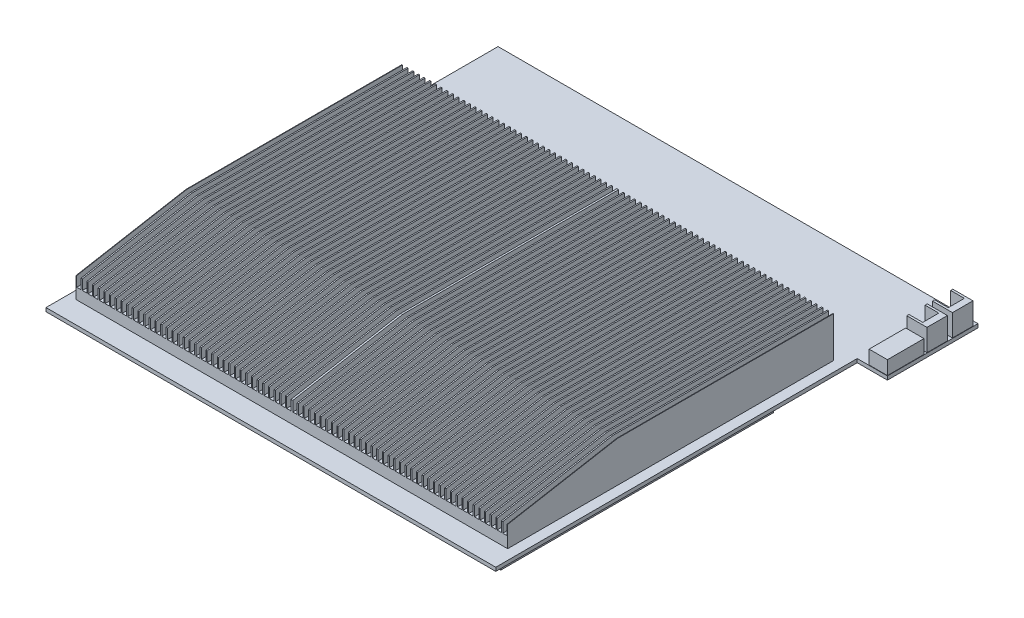
SolidWorks part; units mm, degrees
ref_plane "Front Plane" through (0, 0, 0) normal (0, 0, 1) x (1, 0, 0)
ref_plane "Top Plane" through (0, 0, 0) normal (0, 1, 0) x (1, 0, 0)
ref_plane "Right Plane" through (0, 0, 0) normal (1, 0, 0) x (0, 0, -1)
sketch "Sketch1" plane through (0, 0, 0) normal (0, 1, 0) x (1, 0, 0)
  line L0 (0, 0) -> (0, 247)
  line L1 (0, 247) -> (262.25, 247)
  line L2 (262.25, 247) -> (262.25, 197.5)
  line L3 (262.25, 197.5) -> (245.75, 197.5)
  line L4 (245.75, 197.5) -> (245.75, 0)
  line L5 (245.75, 0) -> (0, 0)
  dimension "D1" = 247
  dimension "D2" = 245.75
  dimension "D3" = 49.5
  dimension "D4" = 16.5
extrude "Boss-Extrude1" add sketch "Sketch1" along normal blind 2
sketch "Sketch2" plane through (0, 2, 0) normal (0, 1, 0) x (1, 0, 0)
  line L0 (245.75, 0) -> (245.75, 197.5) construction
  line L1 (4.5, 190) -> (240.25, 190)
  line L2 (4.5, 190) -> (4.5, 12)
  line L3 (4.5, 12) -> (240.25, 12)
  line L4 (240.25, 190) -> (240.25, 12)
  line L5 (4.5, 190) -> (240.25, 12) construction
  line L6 (4.5, 12) -> (240.25, 190) construction
  line L7 (0, 0) -> (245.75, 0) construction
  line L8 (0, 247) -> (0, 0) construction
  line L9 (262.25, 247) -> (0, 247) construction
  point P4 (122.375, 101)
  dimension "D1" = 5.5
  dimension "D2" = 12
  dimension "D3" = 4.5
  dimension "D4" = 57
extrude "Boss-Extrude2" add sketch "Sketch2" along normal blind 22.2
sketch "Sketch3" plane through (240.25, 0, 0) normal (1, 0, 0) x (0, 0, -1)
  line L0 (12, 13.5) -> (72, 24.2)
  line L1 (12, 24.2) -> (12, 2) construction
  line L2 (12, 24.2) -> (190, 24.2) construction
  line L3 (72, 24.2) -> (12, 24.2)
  line L4 (12, 24.2) -> (12, 13.5)
  dimension "D1" = 60
  dimension "D2" = 10.7
extrude "Cut-Extrude1" cut sketch "Sketch3" against normal up to surface (235.75 mm away) up to face at (4.5, 13.1, -101)
sketch "Sketch5" plane through (0, 0, 0) normal (0, -1, 0) x (1, 0, 0)
  line L0 (7.9691, -163.75) -> (7.9691, -14.75)
  line L6 (233.7585, -14.75) -> (233.7585, -163.75)
  line L9 (7.9691, -163.75) -> (67.4691, -163.75)
  line L10 (67.4691, -163.75) -> (67.4691, -196.5)
  line L11 (67.4691, -196.5) -> (174.2585, -196.5)
  line L12 (174.2585, -196.5) -> (174.2585, -163.75)
  line L13 (174.2585, -163.75) -> (233.7585, -163.75)
  line L14 (233.7585, -14.75) -> (7.9691, -14.75)
  line L15 (0, 0) -> (245.75, 0) construction
  line L16 (262.25, -247) -> (0, -247) construction
  line L18 (122.5508, -211.25) -> (149.8508, -211.25)
  line L19 (122.5508, -211.25) -> (122.5508, -241.5)
  line L20 (122.5508, -241.5) -> (149.8508, -241.5)
  line L21 (149.8508, -211.25) -> (149.8508, -241.5)
  line L22 (122.5508, -211.25) -> (149.8508, -241.5) construction
  line L23 (122.5508, -241.5) -> (149.8508, -211.25) construction
  point P16 (136.2008, -226.375)
  dimension "D1" = 14.75
  dimension "D2" = 50.5
  dimension "D3" = 83.25
  dimension "D4" = 59.5
  dimension "D5" = 5.5
  dimension "D6" = 14.75
  dimension "D7" = 27.3
extrude "Boss-Extrude4" add sketch "Sketch5" along normal blind 12.75
sketch "Sketch6" plane through (0, 0, -190) normal (0, 0, -1) x (-1, 0, 0)
  line L0 (-122.375, 24.2) -> (-122.375, 2) construction
  line L1 (-240.25, 24.2) -> (-4.5, 24.2) construction
  line L2 (-240.25, 2) -> (-4.5, 2) construction
  line L3 (-262.25, 2) -> (0, 2) construction
  line L4 (-122.875, 24.2) -> (-125.275, 24.2)
  line L5 (-122.875, 24.2) -> (-122.875, 8)
  line L6 (-122.875, 8) -> (-125.275, 8)
  line L7 (-125.275, 24.2) -> (-125.275, 8)
  line L8 (-122.875, 24.2) -> (-125.275, 8) construction
  line L9 (-122.875, 8) -> (-125.275, 24.2) construction
  line L10 (-121.875, 8) -> (-119.475, 24.2) construction
  line L11 (-121.875, 24.2) -> (-119.475, 8) construction
  line L12 (-119.475, 24.2) -> (-119.475, 8)
  line L13 (-121.875, 8) -> (-119.475, 8)
  line L14 (-121.875, 24.2) -> (-121.875, 8)
  line L15 (-121.875, 24.2) -> (-119.475, 24.2)
  line L16 (-125.975, 24.2) -> (-128.375, 24.2)
  line L17 (-125.975, 24.2) -> (-125.975, 8)
  line L18 (-125.975, 8) -> (-128.375, 8)
  line L19 (-128.375, 24.2) -> (-128.375, 8)
  line L20 (-125.975, 24.2) -> (-128.375, 8) construction
  line L21 (-125.975, 8) -> (-128.375, 24.2) construction
  line L22 (-129.075, 24.2) -> (-131.475, 24.2)
  line L23 (-129.075, 24.2) -> (-129.075, 8)
  line L24 (-129.075, 8) -> (-131.475, 8)
  line L25 (-131.475, 24.2) -> (-131.475, 8)
  line L26 (-129.075, 24.2) -> (-131.475, 8) construction
  line L27 (-129.075, 8) -> (-131.475, 24.2) construction
  line L28 (-132.175, 24.2) -> (-134.575, 24.2)
  line L29 (-132.175, 24.2) -> (-132.175, 8)
  line L30 (-132.175, 8) -> (-134.575, 8)
  line L31 (-134.575, 24.2) -> (-134.575, 8)
  line L32 (-132.175, 24.2) -> (-134.575, 8) construction
  line L33 (-132.175, 8) -> (-134.575, 24.2) construction
  line L34 (-135.275, 24.2) -> (-137.675, 24.2)
  line L35 (-135.275, 24.2) -> (-135.275, 8)
  line L36 (-135.275, 8) -> (-137.675, 8)
  line L37 (-137.675, 24.2) -> (-137.675, 8)
  line L38 (-135.275, 24.2) -> (-137.675, 8) construction
  line L39 (-135.275, 8) -> (-137.675, 24.2) construction
  line L40 (-138.375, 24.2) -> (-140.775, 24.2)
  line L41 (-138.375, 24.2) -> (-138.375, 8)
  line L42 (-138.375, 8) -> (-140.775, 8)
  line L43 (-140.775, 24.2) -> (-140.775, 8)
  line L44 (-138.375, 24.2) -> (-140.775, 8) construction
  line L45 (-138.375, 8) -> (-140.775, 24.2) construction
  line L46 (-141.475, 24.2) -> (-143.875, 24.2)
  line L47 (-141.475, 24.2) -> (-141.475, 8)
  line L48 (-141.475, 8) -> (-143.875, 8)
  line L49 (-143.875, 24.2) -> (-143.875, 8)
  line L50 (-141.475, 24.2) -> (-143.875, 8) construction
  line L51 (-141.475, 8) -> (-143.875, 24.2) construction
  line L52 (-144.575, 24.2) -> (-146.975, 24.2)
  line L53 (-144.575, 24.2) -> (-144.575, 8)
  line L54 (-144.575, 8) -> (-146.975, 8)
  line L55 (-146.975, 24.2) -> (-146.975, 8)
  line L56 (-144.575, 24.2) -> (-146.975, 8) construction
  line L57 (-144.575, 8) -> (-146.975, 24.2) construction
  line L58 (-147.675, 24.2) -> (-150.075, 24.2)
  line L59 (-147.675, 24.2) -> (-147.675, 8)
  line L60 (-147.675, 8) -> (-150.075, 8)
  line L61 (-150.075, 24.2) -> (-150.075, 8)
  line L62 (-147.675, 24.2) -> (-150.075, 8) construction
  line L63 (-147.675, 8) -> (-150.075, 24.2) construction
  line L64 (-150.775, 24.2) -> (-153.175, 24.2)
  line L65 (-150.775, 24.2) -> (-150.775, 8)
  line L66 (-150.775, 8) -> (-153.175, 8)
  line L67 (-153.175, 24.2) -> (-153.175, 8)
  line L68 (-150.775, 24.2) -> (-153.175, 8) construction
  line L69 (-150.775, 8) -> (-153.175, 24.2) construction
  line L70 (-153.875, 24.2) -> (-156.275, 24.2)
  line L71 (-153.875, 24.2) -> (-153.875, 8)
  line L72 (-153.875, 8) -> (-156.275, 8)
  line L73 (-156.275, 24.2) -> (-156.275, 8)
  line L74 (-153.875, 24.2) -> (-156.275, 8) construction
  line L75 (-153.875, 8) -> (-156.275, 24.2) construction
  line L76 (-156.975, 24.2) -> (-159.375, 24.2)
  line L77 (-156.975, 24.2) -> (-156.975, 8)
  line L78 (-156.975, 8) -> (-159.375, 8)
  line L79 (-159.375, 24.2) -> (-159.375, 8)
  line L80 (-156.975, 24.2) -> (-159.375, 8) construction
  line L81 (-156.975, 8) -> (-159.375, 24.2) construction
  line L82 (-160.075, 24.2) -> (-162.475, 24.2)
  line L83 (-160.075, 24.2) -> (-160.075, 8)
  line L84 (-160.075, 8) -> (-162.475, 8)
  line L85 (-162.475, 24.2) -> (-162.475, 8)
  line L86 (-160.075, 24.2) -> (-162.475, 8) construction
  line L87 (-160.075, 8) -> (-162.475, 24.2) construction
  line L88 (-163.175, 24.2) -> (-165.575, 24.2)
  line L89 (-163.175, 24.2) -> (-163.175, 8)
  line L90 (-163.175, 8) -> (-165.575, 8)
  line L91 (-165.575, 24.2) -> (-165.575, 8)
  line L92 (-163.175, 24.2) -> (-165.575, 8) construction
  line L93 (-163.175, 8) -> (-165.575, 24.2) construction
  line L94 (-166.275, 24.2) -> (-168.675, 24.2)
  line L95 (-166.275, 24.2) -> (-166.275, 8)
  line L96 (-166.275, 8) -> (-168.675, 8)
  line L97 (-168.675, 24.2) -> (-168.675, 8)
  line L98 (-166.275, 24.2) -> (-168.675, 8) construction
  line L99 (-166.275, 8) -> (-168.675, 24.2) construction
  line L100 (-169.375, 24.2) -> (-171.775, 24.2)
  line L101 (-169.375, 24.2) -> (-169.375, 8)
  line L102 (-169.375, 8) -> (-171.775, 8)
  line L103 (-171.775, 24.2) -> (-171.775, 8)
  line L104 (-169.375, 24.2) -> (-171.775, 8) construction
  line L105 (-169.375, 8) -> (-171.775, 24.2) construction
  line L106 (-172.475, 24.2) -> (-174.875, 24.2)
  line L107 (-172.475, 24.2) -> (-172.475, 8)
  line L108 (-172.475, 8) -> (-174.875, 8)
  line L109 (-174.875, 24.2) -> (-174.875, 8)
  line L110 (-172.475, 24.2) -> (-174.875, 8) construction
  line L111 (-172.475, 8) -> (-174.875, 24.2) construction
  line L112 (-175.575, 24.2) -> (-177.975, 24.2)
  line L113 (-175.575, 24.2) -> (-175.575, 8)
  line L114 (-175.575, 8) -> (-177.975, 8)
  line L115 (-177.975, 24.2) -> (-177.975, 8)
  line L116 (-175.575, 24.2) -> (-177.975, 8) construction
  line L117 (-175.575, 8) -> (-177.975, 24.2) construction
  line L118 (-178.675, 24.2) -> (-181.075, 24.2)
  line L119 (-178.675, 24.2) -> (-178.675, 8)
  line L120 (-178.675, 8) -> (-181.075, 8)
  line L121 (-181.075, 24.2) -> (-181.075, 8)
  line L122 (-178.675, 24.2) -> (-181.075, 8) construction
  line L123 (-178.675, 8) -> (-181.075, 24.2) construction
  line L124 (-181.775, 24.2) -> (-184.175, 24.2)
  line L125 (-181.775, 24.2) -> (-181.775, 8)
  line L126 (-181.775, 8) -> (-184.175, 8)
  line L127 (-184.175, 24.2) -> (-184.175, 8)
  line L128 (-181.775, 24.2) -> (-184.175, 8) construction
  line L129 (-181.775, 8) -> (-184.175, 24.2) construction
  line L130 (-184.875, 24.2) -> (-187.275, 24.2)
  line L131 (-184.875, 24.2) -> (-184.875, 8)
  line L132 (-184.875, 8) -> (-187.275, 8)
  line L133 (-187.275, 24.2) -> (-187.275, 8)
  line L134 (-184.875, 24.2) -> (-187.275, 8) construction
  line L135 (-184.875, 8) -> (-187.275, 24.2) construction
  line L136 (-187.975, 24.2) -> (-190.375, 24.2)
  line L137 (-187.975, 24.2) -> (-187.975, 8)
  line L138 (-187.975, 8) -> (-190.375, 8)
  line L139 (-190.375, 24.2) -> (-190.375, 8)
  line L140 (-187.975, 24.2) -> (-190.375, 8) construction
  line L141 (-187.975, 8) -> (-190.375, 24.2) construction
  line L142 (-191.075, 24.2) -> (-193.475, 24.2)
  line L143 (-191.075, 24.2) -> (-191.075, 8)
  line L144 (-191.075, 8) -> (-193.475, 8)
  line L145 (-193.475, 24.2) -> (-193.475, 8)
  line L146 (-191.075, 24.2) -> (-193.475, 8) construction
  line L147 (-191.075, 8) -> (-193.475, 24.2) construction
  line L148 (-194.175, 24.2) -> (-196.575, 24.2)
  line L149 (-194.175, 24.2) -> (-194.175, 8)
  line L150 (-194.175, 8) -> (-196.575, 8)
  line L151 (-196.575, 24.2) -> (-196.575, 8)
  line L152 (-194.175, 24.2) -> (-196.575, 8) construction
  line L153 (-194.175, 8) -> (-196.575, 24.2) construction
  line L154 (-197.275, 24.2) -> (-199.675, 24.2)
  line L155 (-197.275, 24.2) -> (-197.275, 8)
  line L156 (-197.275, 8) -> (-199.675, 8)
  line L157 (-199.675, 24.2) -> (-199.675, 8)
  line L158 (-197.275, 24.2) -> (-199.675, 8) construction
  line L159 (-197.275, 8) -> (-199.675, 24.2) construction
  line L160 (-200.375, 24.2) -> (-202.775, 24.2)
  line L161 (-200.375, 24.2) -> (-200.375, 8)
  line L162 (-200.375, 8) -> (-202.775, 8)
  line L163 (-202.775, 24.2) -> (-202.775, 8)
  line L164 (-200.375, 24.2) -> (-202.775, 8) construction
  line L165 (-200.375, 8) -> (-202.775, 24.2) construction
  line L166 (-203.475, 24.2) -> (-205.875, 24.2)
  line L167 (-203.475, 24.2) -> (-203.475, 8)
  line L168 (-203.475, 8) -> (-205.875, 8)
  line L169 (-205.875, 24.2) -> (-205.875, 8)
  line L170 (-203.475, 24.2) -> (-205.875, 8) construction
  line L171 (-203.475, 8) -> (-205.875, 24.2) construction
  line L172 (-206.575, 24.2) -> (-208.975, 24.2)
  line L173 (-206.575, 24.2) -> (-206.575, 8)
  line L174 (-206.575, 8) -> (-208.975, 8)
  line L175 (-208.975, 24.2) -> (-208.975, 8)
  line L176 (-206.575, 24.2) -> (-208.975, 8) construction
  line L177 (-206.575, 8) -> (-208.975, 24.2) construction
  line L178 (-209.675, 24.2) -> (-212.075, 24.2)
  line L179 (-209.675, 24.2) -> (-209.675, 8)
  line L180 (-209.675, 8) -> (-212.075, 8)
  line L181 (-212.075, 24.2) -> (-212.075, 8)
  line L182 (-209.675, 24.2) -> (-212.075, 8) construction
  line L183 (-209.675, 8) -> (-212.075, 24.2) construction
  line L184 (-212.775, 24.2) -> (-215.175, 24.2)
  line L185 (-212.775, 24.2) -> (-212.775, 8)
  line L186 (-212.775, 8) -> (-215.175, 8)
  line L187 (-215.175, 24.2) -> (-215.175, 8)
  line L188 (-212.775, 24.2) -> (-215.175, 8) construction
  line L189 (-212.775, 8) -> (-215.175, 24.2) construction
  line L190 (-215.875, 24.2) -> (-218.275, 24.2)
  line L191 (-215.875, 24.2) -> (-215.875, 8)
  line L192 (-215.875, 8) -> (-218.275, 8)
  line L193 (-218.275, 24.2) -> (-218.275, 8)
  line L194 (-215.875, 24.2) -> (-218.275, 8) construction
  line L195 (-215.875, 8) -> (-218.275, 24.2) construction
  line L196 (-218.975, 24.2) -> (-221.375, 24.2)
  line L197 (-218.975, 24.2) -> (-218.975, 8)
  line L198 (-218.975, 8) -> (-221.375, 8)
  line L199 (-221.375, 24.2) -> (-221.375, 8)
  line L200 (-218.975, 24.2) -> (-221.375, 8) construction
  line L201 (-218.975, 8) -> (-221.375, 24.2) construction
  line L202 (-222.075, 24.2) -> (-224.475, 24.2)
  line L203 (-222.075, 24.2) -> (-222.075, 8)
  line L204 (-222.075, 8) -> (-224.475, 8)
  line L205 (-224.475, 24.2) -> (-224.475, 8)
  line L206 (-222.075, 24.2) -> (-224.475, 8) construction
  line L207 (-222.075, 8) -> (-224.475, 24.2) construction
  line L208 (-225.175, 24.2) -> (-227.575, 24.2)
  line L209 (-225.175, 24.2) -> (-225.175, 8)
  line L210 (-225.175, 8) -> (-227.575, 8)
  line L211 (-227.575, 24.2) -> (-227.575, 8)
  line L212 (-225.175, 24.2) -> (-227.575, 8) construction
  line L213 (-225.175, 8) -> (-227.575, 24.2) construction
  line L214 (-228.275, 24.2) -> (-230.675, 24.2)
  line L215 (-228.275, 24.2) -> (-228.275, 8)
  line L216 (-228.275, 8) -> (-230.675, 8)
  line L217 (-230.675, 24.2) -> (-230.675, 8)
  line L218 (-228.275, 24.2) -> (-230.675, 8) construction
  line L219 (-228.275, 8) -> (-230.675, 24.2) construction
  line L220 (-231.375, 24.2) -> (-233.775, 24.2)
  line L221 (-231.375, 24.2) -> (-231.375, 8)
  line L222 (-231.375, 8) -> (-233.775, 8)
  line L223 (-233.775, 24.2) -> (-233.775, 8)
  line L224 (-231.375, 24.2) -> (-233.775, 8) construction
  line L225 (-231.375, 8) -> (-233.775, 24.2) construction
  line L226 (-234.475, 24.2) -> (-236.875, 24.2)
  line L227 (-234.475, 24.2) -> (-234.475, 8)
  line L228 (-234.475, 8) -> (-236.875, 8)
  line L229 (-236.875, 24.2) -> (-236.875, 8)
  line L230 (-234.475, 24.2) -> (-236.875, 8) construction
  line L231 (-234.475, 8) -> (-236.875, 24.2) construction
  line L232 (-237.575, 24.2) -> (-239.975, 24.2)
  line L233 (-237.575, 24.2) -> (-237.575, 8)
  line L234 (-237.575, 8) -> (-239.975, 8)
  line L235 (-239.975, 24.2) -> (-239.975, 8)
  line L236 (-237.575, 24.2) -> (-239.975, 8) construction
  line L237 (-237.575, 8) -> (-239.975, 24.2) construction
  line L238 (-116.375, 24.2) -> (-116.375, 8)
  line L239 (-118.775, 8) -> (-116.375, 8)
  line L240 (-118.775, 24.2) -> (-118.775, 8)
  line L241 (-118.775, 24.2) -> (-116.375, 24.2)
  line L242 (-118.775, 8) -> (-116.375, 24.2) construction
  line L243 (-118.775, 24.2) -> (-116.375, 8) construction
  line L244 (-113.275, 24.2) -> (-113.275, 8)
  line L245 (-115.675, 8) -> (-113.275, 8)
  line L246 (-115.675, 24.2) -> (-115.675, 8)
  line L247 (-115.675, 24.2) -> (-113.275, 24.2)
  line L248 (-115.675, 8) -> (-113.275, 24.2) construction
  line L249 (-115.675, 24.2) -> (-113.275, 8) construction
  line L250 (-110.175, 24.2) -> (-110.175, 8)
  line L251 (-112.575, 8) -> (-110.175, 8)
  line L252 (-112.575, 24.2) -> (-112.575, 8)
  line L253 (-112.575, 24.2) -> (-110.175, 24.2)
  line L254 (-112.575, 8) -> (-110.175, 24.2) construction
  line L255 (-112.575, 24.2) -> (-110.175, 8) construction
  line L256 (-107.075, 24.2) -> (-107.075, 8)
  line L257 (-109.475, 8) -> (-107.075, 8)
  line L258 (-109.475, 24.2) -> (-109.475, 8)
  line L259 (-109.475, 24.2) -> (-107.075, 24.2)
  line L260 (-109.475, 8) -> (-107.075, 24.2) construction
  line L261 (-109.475, 24.2) -> (-107.075, 8) construction
  line L262 (-103.975, 24.2) -> (-103.975, 8)
  line L263 (-106.375, 8) -> (-103.975, 8)
  line L264 (-106.375, 24.2) -> (-106.375, 8)
  line L265 (-106.375, 24.2) -> (-103.975, 24.2)
  line L266 (-106.375, 8) -> (-103.975, 24.2) construction
  line L267 (-106.375, 24.2) -> (-103.975, 8) construction
  line L268 (-100.875, 24.2) -> (-100.875, 8)
  line L269 (-103.275, 8) -> (-100.875, 8)
  line L270 (-103.275, 24.2) -> (-103.275, 8)
  line L271 (-103.275, 24.2) -> (-100.875, 24.2)
  line L272 (-103.275, 8) -> (-100.875, 24.2) construction
  line L273 (-103.275, 24.2) -> (-100.875, 8) construction
  line L274 (-97.775, 24.2) -> (-97.775, 8)
  line L275 (-100.175, 8) -> (-97.775, 8)
  line L276 (-100.175, 24.2) -> (-100.175, 8)
  line L277 (-100.175, 24.2) -> (-97.775, 24.2)
  line L278 (-100.175, 8) -> (-97.775, 24.2) construction
  line L279 (-100.175, 24.2) -> (-97.775, 8) construction
  line L280 (-94.675, 24.2) -> (-94.675, 8)
  line L281 (-97.075, 8) -> (-94.675, 8)
  line L282 (-97.075, 24.2) -> (-97.075, 8)
  line L283 (-97.075, 24.2) -> (-94.675, 24.2)
  line L284 (-97.075, 8) -> (-94.675, 24.2) construction
  line L285 (-97.075, 24.2) -> (-94.675, 8) construction
  line L286 (-91.575, 24.2) -> (-91.575, 8)
  line L287 (-93.975, 8) -> (-91.575, 8)
  line L288 (-93.975, 24.2) -> (-93.975, 8)
  line L289 (-93.975, 24.2) -> (-91.575, 24.2)
  line L290 (-93.975, 8) -> (-91.575, 24.2) construction
  line L291 (-93.975, 24.2) -> (-91.575, 8) construction
  line L292 (-88.475, 24.2) -> (-88.475, 8)
  line L293 (-90.875, 8) -> (-88.475, 8)
  line L294 (-90.875, 24.2) -> (-90.875, 8)
  line L295 (-90.875, 24.2) -> (-88.475, 24.2)
  line L296 (-90.875, 8) -> (-88.475, 24.2) construction
  line L297 (-90.875, 24.2) -> (-88.475, 8) construction
  line L298 (-85.375, 24.2) -> (-85.375, 8)
  line L299 (-87.775, 8) -> (-85.375, 8)
  line L300 (-87.775, 24.2) -> (-87.775, 8)
  line L301 (-87.775, 24.2) -> (-85.375, 24.2)
  line L302 (-87.775, 8) -> (-85.375, 24.2) construction
  line L303 (-87.775, 24.2) -> (-85.375, 8) construction
  line L304 (-82.275, 24.2) -> (-82.275, 8)
  line L305 (-84.675, 8) -> (-82.275, 8)
  line L306 (-84.675, 24.2) -> (-84.675, 8)
  line L307 (-84.675, 24.2) -> (-82.275, 24.2)
  line L308 (-84.675, 8) -> (-82.275, 24.2) construction
  line L309 (-84.675, 24.2) -> (-82.275, 8) construction
  line L310 (-79.175, 24.2) -> (-79.175, 8)
  line L311 (-81.575, 8) -> (-79.175, 8)
  line L312 (-81.575, 24.2) -> (-81.575, 8)
  line L313 (-81.575, 24.2) -> (-79.175, 24.2)
  line L314 (-81.575, 8) -> (-79.175, 24.2) construction
  line L315 (-81.575, 24.2) -> (-79.175, 8) construction
  line L316 (-76.075, 24.2) -> (-76.075, 8)
  line L317 (-78.475, 8) -> (-76.075, 8)
  line L318 (-78.475, 24.2) -> (-78.475, 8)
  line L319 (-78.475, 24.2) -> (-76.075, 24.2)
  line L320 (-78.475, 8) -> (-76.075, 24.2) construction
  line L321 (-78.475, 24.2) -> (-76.075, 8) construction
  line L322 (-72.975, 24.2) -> (-72.975, 8)
  line L323 (-75.375, 8) -> (-72.975, 8)
  line L324 (-75.375, 24.2) -> (-75.375, 8)
  line L325 (-75.375, 24.2) -> (-72.975, 24.2)
  line L326 (-75.375, 8) -> (-72.975, 24.2) construction
  line L327 (-75.375, 24.2) -> (-72.975, 8) construction
  line L328 (-69.875, 24.2) -> (-69.875, 8)
  line L329 (-72.275, 8) -> (-69.875, 8)
  line L330 (-72.275, 24.2) -> (-72.275, 8)
  line L331 (-72.275, 24.2) -> (-69.875, 24.2)
  line L332 (-72.275, 8) -> (-69.875, 24.2) construction
  line L333 (-72.275, 24.2) -> (-69.875, 8) construction
  line L334 (-66.775, 24.2) -> (-66.775, 8)
  line L335 (-69.175, 8) -> (-66.775, 8)
  line L336 (-69.175, 24.2) -> (-69.175, 8)
  line L337 (-69.175, 24.2) -> (-66.775, 24.2)
  line L338 (-69.175, 8) -> (-66.775, 24.2) construction
  line L339 (-69.175, 24.2) -> (-66.775, 8) construction
  line L340 (-63.675, 24.2) -> (-63.675, 8)
  line L341 (-66.075, 8) -> (-63.675, 8)
  line L342 (-66.075, 24.2) -> (-66.075, 8)
  line L343 (-66.075, 24.2) -> (-63.675, 24.2)
  line L344 (-66.075, 8) -> (-63.675, 24.2) construction
  line L345 (-66.075, 24.2) -> (-63.675, 8) construction
  line L346 (-60.575, 24.2) -> (-60.575, 8)
  line L347 (-62.975, 8) -> (-60.575, 8)
  line L348 (-62.975, 24.2) -> (-62.975, 8)
  line L349 (-62.975, 24.2) -> (-60.575, 24.2)
  line L350 (-62.975, 8) -> (-60.575, 24.2) construction
  line L351 (-62.975, 24.2) -> (-60.575, 8) construction
  line L352 (-57.475, 24.2) -> (-57.475, 8)
  line L353 (-59.875, 8) -> (-57.475, 8)
  line L354 (-59.875, 24.2) -> (-59.875, 8)
  line L355 (-59.875, 24.2) -> (-57.475, 24.2)
  line L356 (-59.875, 8) -> (-57.475, 24.2) construction
  line L357 (-59.875, 24.2) -> (-57.475, 8) construction
  line L358 (-54.375, 24.2) -> (-54.375, 8)
  line L359 (-56.775, 8) -> (-54.375, 8)
  line L360 (-56.775, 24.2) -> (-56.775, 8)
  line L361 (-56.775, 24.2) -> (-54.375, 24.2)
  line L362 (-56.775, 8) -> (-54.375, 24.2) construction
  line L363 (-56.775, 24.2) -> (-54.375, 8) construction
  line L364 (-51.275, 24.2) -> (-51.275, 8)
  line L365 (-53.675, 8) -> (-51.275, 8)
  line L366 (-53.675, 24.2) -> (-53.675, 8)
  line L367 (-53.675, 24.2) -> (-51.275, 24.2)
  line L368 (-53.675, 8) -> (-51.275, 24.2) construction
  line L369 (-53.675, 24.2) -> (-51.275, 8) construction
  line L370 (-48.175, 24.2) -> (-48.175, 8)
  line L371 (-50.575, 8) -> (-48.175, 8)
  line L372 (-50.575, 24.2) -> (-50.575, 8)
  line L373 (-50.575, 24.2) -> (-48.175, 24.2)
  line L374 (-50.575, 8) -> (-48.175, 24.2) construction
  line L375 (-50.575, 24.2) -> (-48.175, 8) construction
  line L376 (-45.075, 24.2) -> (-45.075, 8)
  line L377 (-47.475, 8) -> (-45.075, 8)
  line L378 (-47.475, 24.2) -> (-47.475, 8)
  line L379 (-47.475, 24.2) -> (-45.075, 24.2)
  line L380 (-47.475, 8) -> (-45.075, 24.2) construction
  line L381 (-47.475, 24.2) -> (-45.075, 8) construction
  line L382 (-41.975, 24.2) -> (-41.975, 8)
  line L383 (-44.375, 8) -> (-41.975, 8)
  line L384 (-44.375, 24.2) -> (-44.375, 8)
  line L385 (-44.375, 24.2) -> (-41.975, 24.2)
  line L386 (-44.375, 8) -> (-41.975, 24.2) construction
  line L387 (-44.375, 24.2) -> (-41.975, 8) construction
  line L388 (-38.875, 24.2) -> (-38.875, 8)
  line L389 (-41.275, 8) -> (-38.875, 8)
  line L390 (-41.275, 24.2) -> (-41.275, 8)
  line L391 (-41.275, 24.2) -> (-38.875, 24.2)
  line L392 (-41.275, 8) -> (-38.875, 24.2) construction
  line L393 (-41.275, 24.2) -> (-38.875, 8) construction
  line L394 (-35.775, 24.2) -> (-35.775, 8)
  line L395 (-38.175, 8) -> (-35.775, 8)
  line L396 (-38.175, 24.2) -> (-38.175, 8)
  line L397 (-38.175, 24.2) -> (-35.775, 24.2)
  line L398 (-38.175, 8) -> (-35.775, 24.2) construction
  line L399 (-38.175, 24.2) -> (-35.775, 8) construction
  line L400 (-32.675, 24.2) -> (-32.675, 8)
  line L401 (-35.075, 8) -> (-32.675, 8)
  line L402 (-35.075, 24.2) -> (-35.075, 8)
  line L403 (-35.075, 24.2) -> (-32.675, 24.2)
  line L404 (-35.075, 8) -> (-32.675, 24.2) construction
  line L405 (-35.075, 24.2) -> (-32.675, 8) construction
  line L406 (-29.575, 24.2) -> (-29.575, 8)
  line L407 (-31.975, 8) -> (-29.575, 8)
  line L408 (-31.975, 24.2) -> (-31.975, 8)
  line L409 (-31.975, 24.2) -> (-29.575, 24.2)
  line L410 (-31.975, 8) -> (-29.575, 24.2) construction
  line L411 (-31.975, 24.2) -> (-29.575, 8) construction
  line L412 (-26.475, 24.2) -> (-26.475, 8)
  line L413 (-28.875, 8) -> (-26.475, 8)
  line L414 (-28.875, 24.2) -> (-28.875, 8)
  line L415 (-28.875, 24.2) -> (-26.475, 24.2)
  line L416 (-28.875, 8) -> (-26.475, 24.2) construction
  line L417 (-28.875, 24.2) -> (-26.475, 8) construction
  line L418 (-23.375, 24.2) -> (-23.375, 8)
  line L419 (-25.775, 8) -> (-23.375, 8)
  line L420 (-25.775, 24.2) -> (-25.775, 8)
  line L421 (-25.775, 24.2) -> (-23.375, 24.2)
  line L422 (-25.775, 8) -> (-23.375, 24.2) construction
  line L423 (-25.775, 24.2) -> (-23.375, 8) construction
  line L424 (-20.275, 24.2) -> (-20.275, 8)
  line L425 (-22.675, 8) -> (-20.275, 8)
  line L426 (-22.675, 24.2) -> (-22.675, 8)
  line L427 (-22.675, 24.2) -> (-20.275, 24.2)
  line L428 (-22.675, 8) -> (-20.275, 24.2) construction
  line L429 (-22.675, 24.2) -> (-20.275, 8) construction
  line L430 (-17.175, 24.2) -> (-17.175, 8)
  line L431 (-19.575, 8) -> (-17.175, 8)
  line L432 (-19.575, 24.2) -> (-19.575, 8)
  line L433 (-19.575, 24.2) -> (-17.175, 24.2)
  line L434 (-19.575, 8) -> (-17.175, 24.2) construction
  line L435 (-19.575, 24.2) -> (-17.175, 8) construction
  line L436 (-14.075, 24.2) -> (-14.075, 8)
  line L437 (-16.475, 8) -> (-14.075, 8)
  line L438 (-16.475, 24.2) -> (-16.475, 8)
  line L439 (-16.475, 24.2) -> (-14.075, 24.2)
  line L440 (-16.475, 8) -> (-14.075, 24.2) construction
  line L441 (-16.475, 24.2) -> (-14.075, 8) construction
  line L442 (-10.975, 24.2) -> (-10.975, 8)
  line L443 (-13.375, 8) -> (-10.975, 8)
  line L444 (-13.375, 24.2) -> (-13.375, 8)
  line L445 (-13.375, 24.2) -> (-10.975, 24.2)
  line L446 (-13.375, 8) -> (-10.975, 24.2) construction
  line L447 (-13.375, 24.2) -> (-10.975, 8) construction
  line L448 (-7.875, 24.2) -> (-7.875, 8)
  line L449 (-10.275, 8) -> (-7.875, 8)
  line L450 (-10.275, 24.2) -> (-10.275, 8)
  line L451 (-10.275, 24.2) -> (-7.875, 24.2)
  line L452 (-10.275, 8) -> (-7.875, 24.2) construction
  line L453 (-10.275, 24.2) -> (-7.875, 8) construction
  line L454 (-4.775, 24.2) -> (-4.775, 8)
  line L455 (-7.175, 8) -> (-4.775, 8)
  line L456 (-7.175, 24.2) -> (-7.175, 8)
  line L457 (-7.175, 24.2) -> (-4.775, 24.2)
  line L458 (-7.175, 8) -> (-4.775, 24.2) construction
  line L459 (-7.175, 24.2) -> (-4.775, 8) construction
  point P10 (-124.075, 16.1)
  point P17 (-120.675, 16.1)
  point P23 (-127.175, 16.1)
  point P28 (-130.275, 16.1)
  point P33 (-133.375, 16.1)
  point P38 (-136.475, 16.1)
  point P43 (-139.575, 16.1)
  point P48 (-142.675, 16.1)
  point P53 (-145.775, 16.1)
  point P58 (-148.875, 16.1)
  point P63 (-151.975, 16.1)
  point P68 (-155.075, 16.1)
  point P73 (-158.175, 16.1)
  point P78 (-161.275, 16.1)
  point P83 (-164.375, 16.1)
  point P88 (-167.475, 16.1)
  point P93 (-170.575, 16.1)
  point P98 (-173.675, 16.1)
  point P103 (-176.775, 16.1)
  point P108 (-179.875, 16.1)
  point P113 (-182.975, 16.1)
  point P118 (-186.075, 16.1)
  point P123 (-189.175, 16.1)
  point P128 (-192.275, 16.1)
  point P133 (-195.375, 16.1)
  point P138 (-198.475, 16.1)
  point P143 (-201.575, 16.1)
  point P148 (-204.675, 16.1)
  point P153 (-207.775, 16.1)
  point P158 (-210.875, 16.1)
  point P163 (-213.975, 16.1)
  point P168 (-217.075, 16.1)
  point P173 (-220.175, 16.1)
  point P178 (-223.275, 16.1)
  point P183 (-226.375, 16.1)
  point P188 (-229.475, 16.1)
  point P193 (-232.575, 16.1)
  point P198 (-235.675, 16.1)
  point P203 (-238.775, 16.1)
  point P209 (-117.575, 16.1)
  point P214 (-114.475, 16.1)
  point P219 (-111.375, 16.1)
  point P224 (-108.275, 16.1)
  point P229 (-105.175, 16.1)
  point P234 (-102.075, 16.1)
  point P239 (-98.975, 16.1)
  point P244 (-95.875, 16.1)
  point P249 (-92.775, 16.1)
  point P254 (-89.675, 16.1)
  point P259 (-86.575, 16.1)
  point P264 (-83.475, 16.1)
  point P269 (-80.375, 16.1)
  point P274 (-77.275, 16.1)
  point P279 (-74.175, 16.1)
  point P284 (-71.075, 16.1)
  point P289 (-67.975, 16.1)
  point P294 (-64.875, 16.1)
  point P299 (-61.775, 16.1)
  point P304 (-58.675, 16.1)
  point P309 (-55.575, 16.1)
  point P314 (-52.475, 16.1)
  point P319 (-49.375, 16.1)
  point P324 (-46.275, 16.1)
  point P329 (-43.175, 16.1)
  point P334 (-40.075, 16.1)
  point P339 (-36.975, 16.1)
  point P344 (-33.875, 16.1)
  point P349 (-30.775, 16.1)
  point P354 (-27.675, 16.1)
  point P359 (-24.575, 16.1)
  point P364 (-21.475, 16.1)
  point P369 (-18.375, 16.1)
  point P374 (-15.275, 16.1)
  point P379 (-12.175, 16.1)
  point P384 (-9.075, 16.1)
  point P389 (-5.975, 16.1)
  dimension "D1" = 1
  dimension "D2" = 6
  dimension "D3" = 2.4
  dimension "D4" = 38
  dimension "D5" = 38
extrude "Cut-Extrude2" cut sketch "Sketch6" against normal through all
sketch "Sketch7" plane through (0, 0, -14.75) normal (0, 0, 1) x (1, 0, 0)
  line L0 (120.8638, 0) -> (120.8638, -12.75) construction
  line L1 (233.7585, 0) -> (7.9691, 0) construction
  line L2 (233.7585, -12.75) -> (7.9691, -12.75) construction
  line L3 (121.8638, -1.9399) -> (124.2638, -12.75) construction
  line L4 (119.8638, -12.75) -> (117.4638, -12.75)
  line L5 (119.8638, -12.75) -> (119.8638, -1.9399)
  line L6 (119.8638, -1.9399) -> (117.4638, -1.9399)
  line L7 (117.4638, -12.75) -> (117.4638, -1.9399)
  line L8 (119.8638, -12.75) -> (117.4638, -1.9399) construction
  line L9 (119.8638, -1.9399) -> (117.4638, -12.75) construction
  line L10 (121.8638, -12.75) -> (124.2638, -1.9399) construction
  line L11 (124.2638, -12.75) -> (124.2638, -1.9399)
  line L12 (121.8638, -1.9399) -> (124.2638, -1.9399)
  line L13 (121.8638, -12.75) -> (121.8638, -1.9399)
  line L14 (121.8638, -12.75) -> (124.2638, -12.75)
  line L15 (127.3638, -12.75) -> (127.3638, -1.9399)
  line L16 (124.9638, -1.9399) -> (127.3638, -1.9399)
  line L17 (124.9638, -12.75) -> (124.9638, -1.9399)
  line L18 (124.9638, -12.75) -> (127.3638, -12.75)
  line L19 (124.9638, -1.9399) -> (127.3638, -12.75) construction
  line L20 (124.9638, -12.75) -> (127.3638, -1.9399) construction
  line L21 (130.4638, -12.75) -> (130.4638, -1.9399)
  line L22 (128.0638, -1.9399) -> (130.4638, -1.9399)
  line L23 (128.0638, -12.75) -> (128.0638, -1.9399)
  line L24 (128.0638, -12.75) -> (130.4638, -12.75)
  line L25 (128.0638, -1.9399) -> (130.4638, -12.75) construction
  line L26 (128.0638, -12.75) -> (130.4638, -1.9399) construction
  line L27 (133.5638, -12.75) -> (133.5638, -1.9399)
  line L28 (131.1638, -1.9399) -> (133.5638, -1.9399)
  line L29 (131.1638, -12.75) -> (131.1638, -1.9399)
  line L30 (131.1638, -12.75) -> (133.5638, -12.75)
  line L31 (131.1638, -1.9399) -> (133.5638, -12.75) construction
  line L32 (131.1638, -12.75) -> (133.5638, -1.9399) construction
  line L33 (136.6638, -12.75) -> (136.6638, -1.9399)
  line L34 (134.2638, -1.9399) -> (136.6638, -1.9399)
  line L35 (134.2638, -12.75) -> (134.2638, -1.9399)
  line L36 (134.2638, -12.75) -> (136.6638, -12.75)
  line L37 (134.2638, -1.9399) -> (136.6638, -12.75) construction
  line L38 (134.2638, -12.75) -> (136.6638, -1.9399) construction
  line L39 (139.7638, -12.75) -> (139.7638, -1.9399)
  line L40 (137.3638, -1.9399) -> (139.7638, -1.9399)
  line L41 (137.3638, -12.75) -> (137.3638, -1.9399)
  line L42 (137.3638, -12.75) -> (139.7638, -12.75)
  line L43 (137.3638, -1.9399) -> (139.7638, -12.75) construction
  line L44 (137.3638, -12.75) -> (139.7638, -1.9399) construction
  line L45 (142.8638, -12.75) -> (142.8638, -1.9399)
  line L46 (140.4638, -1.9399) -> (142.8638, -1.9399)
  line L47 (140.4638, -12.75) -> (140.4638, -1.9399)
  line L48 (140.4638, -12.75) -> (142.8638, -12.75)
  line L49 (140.4638, -1.9399) -> (142.8638, -12.75) construction
  line L50 (140.4638, -12.75) -> (142.8638, -1.9399) construction
  line L51 (145.9638, -12.75) -> (145.9638, -1.9399)
  line L52 (143.5638, -1.9399) -> (145.9638, -1.9399)
  line L53 (143.5638, -12.75) -> (143.5638, -1.9399)
  line L54 (143.5638, -12.75) -> (145.9638, -12.75)
  line L55 (143.5638, -1.9399) -> (145.9638, -12.75) construction
  line L56 (143.5638, -12.75) -> (145.9638, -1.9399) construction
  line L57 (149.0638, -12.75) -> (149.0638, -1.9399)
  line L58 (146.6638, -1.9399) -> (149.0638, -1.9399)
  line L59 (146.6638, -12.75) -> (146.6638, -1.9399)
  line L60 (146.6638, -12.75) -> (149.0638, -12.75)
  line L61 (146.6638, -1.9399) -> (149.0638, -12.75) construction
  line L62 (146.6638, -12.75) -> (149.0638, -1.9399) construction
  line L63 (152.1638, -12.75) -> (152.1638, -1.9399)
  line L64 (149.7638, -1.9399) -> (152.1638, -1.9399)
  line L65 (149.7638, -12.75) -> (149.7638, -1.9399)
  line L66 (149.7638, -12.75) -> (152.1638, -12.75)
  line L67 (149.7638, -1.9399) -> (152.1638, -12.75) construction
  line L68 (149.7638, -12.75) -> (152.1638, -1.9399) construction
  line L69 (155.2638, -12.75) -> (155.2638, -1.9399)
  line L70 (152.8638, -1.9399) -> (155.2638, -1.9399)
  line L71 (152.8638, -12.75) -> (152.8638, -1.9399)
  line L72 (152.8638, -12.75) -> (155.2638, -12.75)
  line L73 (152.8638, -1.9399) -> (155.2638, -12.75) construction
  line L74 (152.8638, -12.75) -> (155.2638, -1.9399) construction
  line L75 (158.3638, -12.75) -> (158.3638, -1.9399)
  line L76 (155.9638, -1.9399) -> (158.3638, -1.9399)
  line L77 (155.9638, -12.75) -> (155.9638, -1.9399)
  line L78 (155.9638, -12.75) -> (158.3638, -12.75)
  line L79 (155.9638, -1.9399) -> (158.3638, -12.75) construction
  line L80 (155.9638, -12.75) -> (158.3638, -1.9399) construction
  line L81 (161.4638, -12.75) -> (161.4638, -1.9399)
  line L82 (159.0638, -1.9399) -> (161.4638, -1.9399)
  line L83 (159.0638, -12.75) -> (159.0638, -1.9399)
  line L84 (159.0638, -12.75) -> (161.4638, -12.75)
  line L85 (159.0638, -1.9399) -> (161.4638, -12.75) construction
  line L86 (159.0638, -12.75) -> (161.4638, -1.9399) construction
  line L87 (164.5638, -12.75) -> (164.5638, -1.9399)
  line L88 (162.1638, -1.9399) -> (164.5638, -1.9399)
  line L89 (162.1638, -12.75) -> (162.1638, -1.9399)
  line L90 (162.1638, -12.75) -> (164.5638, -12.75)
  line L91 (162.1638, -1.9399) -> (164.5638, -12.75) construction
  line L92 (162.1638, -12.75) -> (164.5638, -1.9399) construction
  line L93 (167.6638, -12.75) -> (167.6638, -1.9399)
  line L94 (165.2638, -1.9399) -> (167.6638, -1.9399)
  line L95 (165.2638, -12.75) -> (165.2638, -1.9399)
  line L96 (165.2638, -12.75) -> (167.6638, -12.75)
  line L97 (165.2638, -1.9399) -> (167.6638, -12.75) construction
  line L98 (165.2638, -12.75) -> (167.6638, -1.9399) construction
  line L99 (170.7638, -12.75) -> (170.7638, -1.9399)
  line L100 (168.3638, -1.9399) -> (170.7638, -1.9399)
  line L101 (168.3638, -12.75) -> (168.3638, -1.9399)
  line L102 (168.3638, -12.75) -> (170.7638, -12.75)
  line L103 (168.3638, -1.9399) -> (170.7638, -12.75) construction
  line L104 (168.3638, -12.75) -> (170.7638, -1.9399) construction
  line L105 (173.8638, -12.75) -> (173.8638, -1.9399)
  line L106 (171.4638, -1.9399) -> (173.8638, -1.9399)
  line L107 (171.4638, -12.75) -> (171.4638, -1.9399)
  line L108 (171.4638, -12.75) -> (173.8638, -12.75)
  line L109 (171.4638, -1.9399) -> (173.8638, -12.75) construction
  line L110 (171.4638, -12.75) -> (173.8638, -1.9399) construction
  line L111 (176.9638, -12.75) -> (176.9638, -1.9399)
  line L112 (174.5638, -1.9399) -> (176.9638, -1.9399)
  line L113 (174.5638, -12.75) -> (174.5638, -1.9399)
  line L114 (174.5638, -12.75) -> (176.9638, -12.75)
  line L115 (174.5638, -1.9399) -> (176.9638, -12.75) construction
  line L116 (174.5638, -12.75) -> (176.9638, -1.9399) construction
  line L117 (180.0638, -12.75) -> (180.0638, -1.9399)
  line L118 (177.6638, -1.9399) -> (180.0638, -1.9399)
  line L119 (177.6638, -12.75) -> (177.6638, -1.9399)
  line L120 (177.6638, -12.75) -> (180.0638, -12.75)
  line L121 (177.6638, -1.9399) -> (180.0638, -12.75) construction
  line L122 (177.6638, -12.75) -> (180.0638, -1.9399) construction
  line L123 (183.1638, -12.75) -> (183.1638, -1.9399)
  line L124 (180.7638, -1.9399) -> (183.1638, -1.9399)
  line L125 (180.7638, -12.75) -> (180.7638, -1.9399)
  line L126 (180.7638, -12.75) -> (183.1638, -12.75)
  line L127 (180.7638, -1.9399) -> (183.1638, -12.75) construction
  line L128 (180.7638, -12.75) -> (183.1638, -1.9399) construction
  line L129 (186.2638, -12.75) -> (186.2638, -1.9399)
  line L130 (183.8638, -1.9399) -> (186.2638, -1.9399)
  line L131 (183.8638, -12.75) -> (183.8638, -1.9399)
  line L132 (183.8638, -12.75) -> (186.2638, -12.75)
  line L133 (183.8638, -1.9399) -> (186.2638, -12.75) construction
  line L134 (183.8638, -12.75) -> (186.2638, -1.9399) construction
  line L135 (189.3638, -12.75) -> (189.3638, -1.9399)
  line L136 (186.9638, -1.9399) -> (189.3638, -1.9399)
  line L137 (186.9638, -12.75) -> (186.9638, -1.9399)
  line L138 (186.9638, -12.75) -> (189.3638, -12.75)
  line L139 (186.9638, -1.9399) -> (189.3638, -12.75) construction
  line L140 (186.9638, -12.75) -> (189.3638, -1.9399) construction
  line L141 (192.4638, -12.75) -> (192.4638, -1.9399)
  line L142 (190.0638, -1.9399) -> (192.4638, -1.9399)
  line L143 (190.0638, -12.75) -> (190.0638, -1.9399)
  line L144 (190.0638, -12.75) -> (192.4638, -12.75)
  line L145 (190.0638, -1.9399) -> (192.4638, -12.75) construction
  line L146 (190.0638, -12.75) -> (192.4638, -1.9399) construction
  line L147 (195.5638, -12.75) -> (195.5638, -1.9399)
  line L148 (193.1638, -1.9399) -> (195.5638, -1.9399)
  line L149 (193.1638, -12.75) -> (193.1638, -1.9399)
  line L150 (193.1638, -12.75) -> (195.5638, -12.75)
  line L151 (193.1638, -1.9399) -> (195.5638, -12.75) construction
  line L152 (193.1638, -12.75) -> (195.5638, -1.9399) construction
  line L153 (198.6638, -12.75) -> (198.6638, -1.9399)
  line L154 (196.2638, -1.9399) -> (198.6638, -1.9399)
  line L155 (196.2638, -12.75) -> (196.2638, -1.9399)
  line L156 (196.2638, -12.75) -> (198.6638, -12.75)
  line L157 (196.2638, -1.9399) -> (198.6638, -12.75) construction
  line L158 (196.2638, -12.75) -> (198.6638, -1.9399) construction
  line L159 (201.7638, -12.75) -> (201.7638, -1.9399)
  line L160 (199.3638, -1.9399) -> (201.7638, -1.9399)
  line L161 (199.3638, -12.75) -> (199.3638, -1.9399)
  line L162 (199.3638, -12.75) -> (201.7638, -12.75)
  line L163 (199.3638, -1.9399) -> (201.7638, -12.75) construction
  line L164 (199.3638, -12.75) -> (201.7638, -1.9399) construction
  line L165 (204.8638, -12.75) -> (204.8638, -1.9399)
  line L166 (202.4638, -1.9399) -> (204.8638, -1.9399)
  line L167 (202.4638, -12.75) -> (202.4638, -1.9399)
  line L168 (202.4638, -12.75) -> (204.8638, -12.75)
  line L169 (202.4638, -1.9399) -> (204.8638, -12.75) construction
  line L170 (202.4638, -12.75) -> (204.8638, -1.9399) construction
  line L171 (207.9638, -12.75) -> (207.9638, -1.9399)
  line L172 (205.5638, -1.9399) -> (207.9638, -1.9399)
  line L173 (205.5638, -12.75) -> (205.5638, -1.9399)
  line L174 (205.5638, -12.75) -> (207.9638, -12.75)
  line L175 (205.5638, -1.9399) -> (207.9638, -12.75) construction
  line L176 (205.5638, -12.75) -> (207.9638, -1.9399) construction
  line L177 (211.0638, -12.75) -> (211.0638, -1.9399)
  line L178 (208.6638, -1.9399) -> (211.0638, -1.9399)
  line L179 (208.6638, -12.75) -> (208.6638, -1.9399)
  line L180 (208.6638, -12.75) -> (211.0638, -12.75)
  line L181 (208.6638, -1.9399) -> (211.0638, -12.75) construction
  line L182 (208.6638, -12.75) -> (211.0638, -1.9399) construction
  line L183 (214.1638, -12.75) -> (214.1638, -1.9399)
  line L184 (211.7638, -1.9399) -> (214.1638, -1.9399)
  line L185 (211.7638, -12.75) -> (211.7638, -1.9399)
  line L186 (211.7638, -12.75) -> (214.1638, -12.75)
  line L187 (211.7638, -1.9399) -> (214.1638, -12.75) construction
  line L188 (211.7638, -12.75) -> (214.1638, -1.9399) construction
  line L189 (217.2638, -12.75) -> (217.2638, -1.9399)
  line L190 (214.8638, -1.9399) -> (217.2638, -1.9399)
  line L191 (214.8638, -12.75) -> (214.8638, -1.9399)
  line L192 (214.8638, -12.75) -> (217.2638, -12.75)
  line L193 (214.8638, -1.9399) -> (217.2638, -12.75) construction
  line L194 (214.8638, -12.75) -> (217.2638, -1.9399) construction
  line L195 (220.3638, -12.75) -> (220.3638, -1.9399)
  line L196 (217.9638, -1.9399) -> (220.3638, -1.9399)
  line L197 (217.9638, -12.75) -> (217.9638, -1.9399)
  line L198 (217.9638, -12.75) -> (220.3638, -12.75)
  line L199 (217.9638, -1.9399) -> (220.3638, -12.75) construction
  line L200 (217.9638, -12.75) -> (220.3638, -1.9399) construction
  line L201 (223.4638, -12.75) -> (223.4638, -1.9399)
  line L202 (221.0638, -1.9399) -> (223.4638, -1.9399)
  line L203 (221.0638, -12.75) -> (221.0638, -1.9399)
  line L204 (221.0638, -12.75) -> (223.4638, -12.75)
  line L205 (221.0638, -1.9399) -> (223.4638, -12.75) construction
  line L206 (221.0638, -12.75) -> (223.4638, -1.9399) construction
  line L207 (226.5638, -12.75) -> (226.5638, -1.9399)
  line L208 (224.1638, -1.9399) -> (226.5638, -1.9399)
  line L209 (224.1638, -12.75) -> (224.1638, -1.9399)
  line L210 (224.1638, -12.75) -> (226.5638, -12.75)
  line L211 (224.1638, -1.9399) -> (226.5638, -12.75) construction
  line L212 (224.1638, -12.75) -> (226.5638, -1.9399) construction
  line L213 (229.6638, -12.75) -> (229.6638, -1.9399)
  line L214 (227.2638, -1.9399) -> (229.6638, -1.9399)
  line L215 (227.2638, -12.75) -> (227.2638, -1.9399)
  line L216 (227.2638, -12.75) -> (229.6638, -12.75)
  line L217 (227.2638, -1.9399) -> (229.6638, -12.75) construction
  line L218 (227.2638, -12.75) -> (229.6638, -1.9399) construction
  line L219 (232.7638, -12.75) -> (232.7638, -1.9399)
  line L220 (230.3638, -1.9399) -> (232.7638, -1.9399)
  line L221 (230.3638, -12.75) -> (230.3638, -1.9399)
  line L222 (230.3638, -12.75) -> (232.7638, -12.75)
  line L223 (230.3638, -1.9399) -> (232.7638, -12.75) construction
  line L224 (230.3638, -12.75) -> (232.7638, -1.9399) construction
  line L225 (116.7638, -12.75) -> (114.3638, -12.75)
  line L226 (116.7638, -12.75) -> (116.7638, -1.9399)
  line L227 (116.7638, -1.9399) -> (114.3638, -1.9399)
  line L228 (114.3638, -12.75) -> (114.3638, -1.9399)
  line L229 (116.7638, -12.75) -> (114.3638, -1.9399) construction
  line L230 (116.7638, -1.9399) -> (114.3638, -12.75) construction
  line L231 (113.6638, -12.75) -> (111.2638, -12.75)
  line L232 (113.6638, -12.75) -> (113.6638, -1.9399)
  line L233 (113.6638, -1.9399) -> (111.2638, -1.9399)
  line L234 (111.2638, -12.75) -> (111.2638, -1.9399)
  line L235 (113.6638, -12.75) -> (111.2638, -1.9399) construction
  line L236 (113.6638, -1.9399) -> (111.2638, -12.75) construction
  line L237 (110.5638, -12.75) -> (108.1638, -12.75)
  line L238 (110.5638, -12.75) -> (110.5638, -1.9399)
  line L239 (110.5638, -1.9399) -> (108.1638, -1.9399)
  line L240 (108.1638, -12.75) -> (108.1638, -1.9399)
  line L241 (110.5638, -12.75) -> (108.1638, -1.9399) construction
  line L242 (110.5638, -1.9399) -> (108.1638, -12.75) construction
  line L243 (107.4638, -12.75) -> (105.0638, -12.75)
  line L244 (107.4638, -12.75) -> (107.4638, -1.9399)
  line L245 (107.4638, -1.9399) -> (105.0638, -1.9399)
  line L246 (105.0638, -12.75) -> (105.0638, -1.9399)
  line L247 (107.4638, -12.75) -> (105.0638, -1.9399) construction
  line L248 (107.4638, -1.9399) -> (105.0638, -12.75) construction
  line L249 (104.3638, -12.75) -> (101.9638, -12.75)
  line L250 (104.3638, -12.75) -> (104.3638, -1.9399)
  line L251 (104.3638, -1.9399) -> (101.9638, -1.9399)
  line L252 (101.9638, -12.75) -> (101.9638, -1.9399)
  line L253 (104.3638, -12.75) -> (101.9638, -1.9399) construction
  line L254 (104.3638, -1.9399) -> (101.9638, -12.75) construction
  line L255 (101.2638, -12.75) -> (98.8638, -12.75)
  line L256 (101.2638, -12.75) -> (101.2638, -1.9399)
  line L257 (101.2638, -1.9399) -> (98.8638, -1.9399)
  line L258 (98.8638, -12.75) -> (98.8638, -1.9399)
  line L259 (101.2638, -12.75) -> (98.8638, -1.9399) construction
  line L260 (101.2638, -1.9399) -> (98.8638, -12.75) construction
  line L261 (98.1638, -12.75) -> (95.7638, -12.75)
  line L262 (98.1638, -12.75) -> (98.1638, -1.9399)
  line L263 (98.1638, -1.9399) -> (95.7638, -1.9399)
  line L264 (95.7638, -12.75) -> (95.7638, -1.9399)
  line L265 (98.1638, -12.75) -> (95.7638, -1.9399) construction
  line L266 (98.1638, -1.9399) -> (95.7638, -12.75) construction
  line L267 (95.0638, -12.75) -> (92.6638, -12.75)
  line L268 (95.0638, -12.75) -> (95.0638, -1.9399)
  line L269 (95.0638, -1.9399) -> (92.6638, -1.9399)
  line L270 (92.6638, -12.75) -> (92.6638, -1.9399)
  line L271 (95.0638, -12.75) -> (92.6638, -1.9399) construction
  line L272 (95.0638, -1.9399) -> (92.6638, -12.75) construction
  line L273 (91.9638, -12.75) -> (89.5638, -12.75)
  line L274 (91.9638, -12.75) -> (91.9638, -1.9399)
  line L275 (91.9638, -1.9399) -> (89.5638, -1.9399)
  line L276 (89.5638, -12.75) -> (89.5638, -1.9399)
  line L277 (91.9638, -12.75) -> (89.5638, -1.9399) construction
  line L278 (91.9638, -1.9399) -> (89.5638, -12.75) construction
  line L279 (88.8638, -12.75) -> (86.4638, -12.75)
  line L280 (88.8638, -12.75) -> (88.8638, -1.9399)
  line L281 (88.8638, -1.9399) -> (86.4638, -1.9399)
  line L282 (86.4638, -12.75) -> (86.4638, -1.9399)
  line L283 (88.8638, -12.75) -> (86.4638, -1.9399) construction
  line L284 (88.8638, -1.9399) -> (86.4638, -12.75) construction
  line L285 (85.7638, -12.75) -> (83.3638, -12.75)
  line L286 (85.7638, -12.75) -> (85.7638, -1.9399)
  line L287 (85.7638, -1.9399) -> (83.3638, -1.9399)
  line L288 (83.3638, -12.75) -> (83.3638, -1.9399)
  line L289 (85.7638, -12.75) -> (83.3638, -1.9399) construction
  line L290 (85.7638, -1.9399) -> (83.3638, -12.75) construction
  line L291 (82.6638, -12.75) -> (80.2638, -12.75)
  line L292 (82.6638, -12.75) -> (82.6638, -1.9399)
  line L293 (82.6638, -1.9399) -> (80.2638, -1.9399)
  line L294 (80.2638, -12.75) -> (80.2638, -1.9399)
  line L295 (82.6638, -12.75) -> (80.2638, -1.9399) construction
  line L296 (82.6638, -1.9399) -> (80.2638, -12.75) construction
  line L297 (79.5638, -12.75) -> (77.1638, -12.75)
  line L298 (79.5638, -12.75) -> (79.5638, -1.9399)
  line L299 (79.5638, -1.9399) -> (77.1638, -1.9399)
  line L300 (77.1638, -12.75) -> (77.1638, -1.9399)
  line L301 (79.5638, -12.75) -> (77.1638, -1.9399) construction
  line L302 (79.5638, -1.9399) -> (77.1638, -12.75) construction
  line L303 (76.4638, -12.75) -> (74.0638, -12.75)
  line L304 (76.4638, -12.75) -> (76.4638, -1.9399)
  line L305 (76.4638, -1.9399) -> (74.0638, -1.9399)
  line L306 (74.0638, -12.75) -> (74.0638, -1.9399)
  line L307 (76.4638, -12.75) -> (74.0638, -1.9399) construction
  line L308 (76.4638, -1.9399) -> (74.0638, -12.75) construction
  line L309 (73.3638, -12.75) -> (70.9638, -12.75)
  line L310 (73.3638, -12.75) -> (73.3638, -1.9399)
  line L311 (73.3638, -1.9399) -> (70.9638, -1.9399)
  line L312 (70.9638, -12.75) -> (70.9638, -1.9399)
  line L313 (73.3638, -12.75) -> (70.9638, -1.9399) construction
  line L314 (73.3638, -1.9399) -> (70.9638, -12.75) construction
  line L315 (70.2638, -12.75) -> (67.8638, -12.75)
  line L316 (70.2638, -12.75) -> (70.2638, -1.9399)
  line L317 (70.2638, -1.9399) -> (67.8638, -1.9399)
  line L318 (67.8638, -12.75) -> (67.8638, -1.9399)
  line L319 (70.2638, -12.75) -> (67.8638, -1.9399) construction
  line L320 (70.2638, -1.9399) -> (67.8638, -12.75) construction
  line L321 (67.1638, -12.75) -> (64.7638, -12.75)
  line L322 (67.1638, -12.75) -> (67.1638, -1.9399)
  line L323 (67.1638, -1.9399) -> (64.7638, -1.9399)
  line L324 (64.7638, -12.75) -> (64.7638, -1.9399)
  line L325 (67.1638, -12.75) -> (64.7638, -1.9399) construction
  line L326 (67.1638, -1.9399) -> (64.7638, -12.75) construction
  line L327 (64.0638, -12.75) -> (61.6638, -12.75)
  line L328 (64.0638, -12.75) -> (64.0638, -1.9399)
  line L329 (64.0638, -1.9399) -> (61.6638, -1.9399)
  line L330 (61.6638, -12.75) -> (61.6638, -1.9399)
  line L331 (64.0638, -12.75) -> (61.6638, -1.9399) construction
  line L332 (64.0638, -1.9399) -> (61.6638, -12.75) construction
  line L333 (60.9638, -12.75) -> (58.5638, -12.75)
  line L334 (60.9638, -12.75) -> (60.9638, -1.9399)
  line L335 (60.9638, -1.9399) -> (58.5638, -1.9399)
  line L336 (58.5638, -12.75) -> (58.5638, -1.9399)
  line L337 (60.9638, -12.75) -> (58.5638, -1.9399) construction
  line L338 (60.9638, -1.9399) -> (58.5638, -12.75) construction
  line L339 (57.8638, -12.75) -> (55.4638, -12.75)
  line L340 (57.8638, -12.75) -> (57.8638, -1.9399)
  line L341 (57.8638, -1.9399) -> (55.4638, -1.9399)
  line L342 (55.4638, -12.75) -> (55.4638, -1.9399)
  line L343 (57.8638, -12.75) -> (55.4638, -1.9399) construction
  line L344 (57.8638, -1.9399) -> (55.4638, -12.75) construction
  line L345 (54.7638, -12.75) -> (52.3638, -12.75)
  line L346 (54.7638, -12.75) -> (54.7638, -1.9399)
  line L347 (54.7638, -1.9399) -> (52.3638, -1.9399)
  line L348 (52.3638, -12.75) -> (52.3638, -1.9399)
  line L349 (54.7638, -12.75) -> (52.3638, -1.9399) construction
  line L350 (54.7638, -1.9399) -> (52.3638, -12.75) construction
  line L351 (51.6638, -12.75) -> (49.2638, -12.75)
  line L352 (51.6638, -12.75) -> (51.6638, -1.9399)
  line L353 (51.6638, -1.9399) -> (49.2638, -1.9399)
  line L354 (49.2638, -12.75) -> (49.2638, -1.9399)
  line L355 (51.6638, -12.75) -> (49.2638, -1.9399) construction
  line L356 (51.6638, -1.9399) -> (49.2638, -12.75) construction
  line L357 (48.5638, -12.75) -> (46.1638, -12.75)
  line L358 (48.5638, -12.75) -> (48.5638, -1.9399)
  line L359 (48.5638, -1.9399) -> (46.1638, -1.9399)
  line L360 (46.1638, -12.75) -> (46.1638, -1.9399)
  line L361 (48.5638, -12.75) -> (46.1638, -1.9399) construction
  line L362 (48.5638, -1.9399) -> (46.1638, -12.75) construction
  line L363 (45.4638, -12.75) -> (43.0638, -12.75)
  line L364 (45.4638, -12.75) -> (45.4638, -1.9399)
  line L365 (45.4638, -1.9399) -> (43.0638, -1.9399)
  line L366 (43.0638, -12.75) -> (43.0638, -1.9399)
  line L367 (45.4638, -12.75) -> (43.0638, -1.9399) construction
  line L368 (45.4638, -1.9399) -> (43.0638, -12.75) construction
  line L369 (42.3638, -12.75) -> (39.9638, -12.75)
  line L370 (42.3638, -12.75) -> (42.3638, -1.9399)
  line L371 (42.3638, -1.9399) -> (39.9638, -1.9399)
  line L372 (39.9638, -12.75) -> (39.9638, -1.9399)
  line L373 (42.3638, -12.75) -> (39.9638, -1.9399) construction
  line L374 (42.3638, -1.9399) -> (39.9638, -12.75) construction
  line L375 (39.2638, -12.75) -> (36.8638, -12.75)
  line L376 (39.2638, -12.75) -> (39.2638, -1.9399)
  line L377 (39.2638, -1.9399) -> (36.8638, -1.9399)
  line L378 (36.8638, -12.75) -> (36.8638, -1.9399)
  line L379 (39.2638, -12.75) -> (36.8638, -1.9399) construction
  line L380 (39.2638, -1.9399) -> (36.8638, -12.75) construction
  line L381 (36.1638, -12.75) -> (33.7638, -12.75)
  line L382 (36.1638, -12.75) -> (36.1638, -1.9399)
  line L383 (36.1638, -1.9399) -> (33.7638, -1.9399)
  line L384 (33.7638, -12.75) -> (33.7638, -1.9399)
  line L385 (36.1638, -12.75) -> (33.7638, -1.9399) construction
  line L386 (36.1638, -1.9399) -> (33.7638, -12.75) construction
  line L387 (33.0638, -12.75) -> (30.6638, -12.75)
  line L388 (33.0638, -12.75) -> (33.0638, -1.9399)
  line L389 (33.0638, -1.9399) -> (30.6638, -1.9399)
  line L390 (30.6638, -12.75) -> (30.6638, -1.9399)
  line L391 (33.0638, -12.75) -> (30.6638, -1.9399) construction
  line L392 (33.0638, -1.9399) -> (30.6638, -12.75) construction
  line L393 (29.9638, -12.75) -> (27.5638, -12.75)
  line L394 (29.9638, -12.75) -> (29.9638, -1.9399)
  line L395 (29.9638, -1.9399) -> (27.5638, -1.9399)
  line L396 (27.5638, -12.75) -> (27.5638, -1.9399)
  line L397 (29.9638, -12.75) -> (27.5638, -1.9399) construction
  line L398 (29.9638, -1.9399) -> (27.5638, -12.75) construction
  line L399 (26.8638, -12.75) -> (24.4638, -12.75)
  line L400 (26.8638, -12.75) -> (26.8638, -1.9399)
  line L401 (26.8638, -1.9399) -> (24.4638, -1.9399)
  line L402 (24.4638, -12.75) -> (24.4638, -1.9399)
  line L403 (26.8638, -12.75) -> (24.4638, -1.9399) construction
  line L404 (26.8638, -1.9399) -> (24.4638, -12.75) construction
  line L405 (23.7638, -12.75) -> (21.3638, -12.75)
  line L406 (23.7638, -12.75) -> (23.7638, -1.9399)
  line L407 (23.7638, -1.9399) -> (21.3638, -1.9399)
  line L408 (21.3638, -12.75) -> (21.3638, -1.9399)
  line L409 (23.7638, -12.75) -> (21.3638, -1.9399) construction
  line L410 (23.7638, -1.9399) -> (21.3638, -12.75) construction
  line L411 (20.6638, -12.75) -> (18.2638, -12.75)
  line L412 (20.6638, -12.75) -> (20.6638, -1.9399)
  line L413 (20.6638, -1.9399) -> (18.2638, -1.9399)
  line L414 (18.2638, -12.75) -> (18.2638, -1.9399)
  line L415 (20.6638, -12.75) -> (18.2638, -1.9399) construction
  line L416 (20.6638, -1.9399) -> (18.2638, -12.75) construction
  line L417 (17.5638, -12.75) -> (15.1638, -12.75)
  line L418 (17.5638, -12.75) -> (17.5638, -1.9399)
  line L419 (17.5638, -1.9399) -> (15.1638, -1.9399)
  line L420 (15.1638, -12.75) -> (15.1638, -1.9399)
  line L421 (17.5638, -12.75) -> (15.1638, -1.9399) construction
  line L422 (17.5638, -1.9399) -> (15.1638, -12.75) construction
  line L423 (14.4638, -12.75) -> (12.0638, -12.75)
  line L424 (14.4638, -12.75) -> (14.4638, -1.9399)
  line L425 (14.4638, -1.9399) -> (12.0638, -1.9399)
  line L426 (12.0638, -12.75) -> (12.0638, -1.9399)
  line L427 (14.4638, -12.75) -> (12.0638, -1.9399) construction
  line L428 (14.4638, -1.9399) -> (12.0638, -12.75) construction
  line L429 (11.3638, -12.75) -> (8.9638, -12.75)
  line L430 (11.3638, -12.75) -> (11.3638, -1.9399)
  line L431 (11.3638, -1.9399) -> (8.9638, -1.9399)
  line L432 (8.9638, -12.75) -> (8.9638, -1.9399)
  line L433 (11.3638, -12.75) -> (8.9638, -1.9399) construction
  line L434 (11.3638, -1.9399) -> (8.9638, -12.75) construction
  point P10 (118.6638, -7.3449)
  point P15 (123.0638, -7.3449)
  point P21 (126.1638, -7.3449)
  point P26 (129.2638, -7.3449)
  point P31 (132.3638, -7.3449)
  point P36 (135.4638, -7.3449)
  point P41 (138.5638, -7.3449)
  point P46 (141.6638, -7.3449)
  point P51 (144.7638, -7.3449)
  point P56 (147.8638, -7.3449)
  point P61 (150.9638, -7.3449)
  point P66 (154.0638, -7.3449)
  point P71 (157.1638, -7.3449)
  point P76 (160.2638, -7.3449)
  point P81 (163.3638, -7.3449)
  point P86 (166.4638, -7.3449)
  point P91 (169.5638, -7.3449)
  point P96 (172.6638, -7.3449)
  point P101 (175.7638, -7.3449)
  point P106 (178.8638, -7.3449)
  point P111 (181.9638, -7.3449)
  point P116 (185.0638, -7.3449)
  point P121 (188.1638, -7.3449)
  point P126 (191.2638, -7.3449)
  point P131 (194.3638, -7.3449)
  point P136 (197.4638, -7.3449)
  point P141 (200.5638, -7.3449)
  point P146 (203.6638, -7.3449)
  point P151 (206.7638, -7.3449)
  point P156 (209.8638, -7.3449)
  point P161 (212.9638, -7.3449)
  point P166 (216.0638, -7.3449)
  point P171 (219.1638, -7.3449)
  point P176 (222.2638, -7.3449)
  point P181 (225.3638, -7.3449)
  point P186 (228.4638, -7.3449)
  point P191 (231.5638, -7.3449)
  point P197 (115.5638, -7.3449)
  point P202 (112.4638, -7.3449)
  point P207 (109.3638, -7.3449)
  point P212 (106.2638, -7.3449)
  point P217 (103.1638, -7.3449)
  point P222 (100.0638, -7.3449)
  point P227 (96.9638, -7.3449)
  point P232 (93.8638, -7.3449)
  point P237 (90.7638, -7.3449)
  point P242 (87.6638, -7.3449)
  point P247 (84.5638, -7.3449)
  point P252 (81.4638, -7.3449)
  point P257 (78.3638, -7.3449)
  point P262 (75.2638, -7.3449)
  point P267 (72.1638, -7.3449)
  point P272 (69.0638, -7.3449)
  point P277 (65.9638, -7.3449)
  point P282 (62.8638, -7.3449)
  point P287 (59.7638, -7.3449)
  point P292 (56.6638, -7.3449)
  point P297 (53.5638, -7.3449)
  point P302 (50.4638, -7.3449)
  point P307 (47.3638, -7.3449)
  point P312 (44.2638, -7.3449)
  point P317 (41.1638, -7.3449)
  point P322 (38.0638, -7.3449)
  point P327 (34.9638, -7.3449)
  point P332 (31.8638, -7.3449)
  point P337 (28.7638, -7.3449)
  point P342 (25.6638, -7.3449)
  point P347 (22.5638, -7.3449)
  point P352 (19.4638, -7.3449)
  point P357 (16.3638, -7.3449)
  point P362 (13.2638, -7.3449)
  point P367 (10.1638, -7.3449)
  dimension "D1" = 2.4
  dimension "D2" = 1
  dimension "D3" = 36
  dimension "D4" = 36
extrude "Cut-Extrude3" cut sketch "Sketch7" against normal through all
ref_plane "Plane1" through (0, 2.2, 0) normal (0, 1, 0) x (1, 0, 0)
sketch "Sketch8" plane through (0, 2.2, 0) normal (0, 1, 0) x (1, 0, 0)
  line L1 (262.25, 197.5) -> (252.25, 197.5)
  line L2 (262.25, 197.5) -> (262.25, 217.5)
  line L3 (262.25, 217.5) -> (252.25, 217.5)
  line L4 (252.25, 197.5) -> (252.25, 217.5)
  line L5 (262.25, 197.5) -> (252.25, 217.5) construction
  line L6 (262.25, 217.5) -> (252.25, 197.5) construction
  point P4 (257.25, 207.5)
  dimension "D1" = 10
  dimension "D2" = 20
extrude "Boss-Extrude5" add sketch "Sketch8" along normal blind 7.5 separate body
sketch "Sketch9" plane through (0, 2.2, 0) normal (0, 1, 0) x (1, 0, 0)
  line L0 (262.25, 197.5) -> (262.25, 247) construction
  line L1 (262.25, 219.1) -> (251.25, 219.1)
  line L2 (262.25, 219.1) -> (262.25, 230.3)
  line L3 (262.25, 230.3) -> (251.25, 230.3)
  line L4 (251.25, 219.1) -> (251.25, 230.3)
  line L5 (262.25, 219.1) -> (251.25, 230.3) construction
  line L6 (262.25, 230.3) -> (251.25, 219.1) construction
  line L7 (262.25, 247) -> (0, 247) construction
  line L8 (262.25, 233.05) -> (251.25, 233.05)
  line L9 (262.25, 233.05) -> (262.25, 244.25)
  line L10 (262.25, 244.25) -> (251.25, 244.25)
  line L11 (251.25, 233.05) -> (251.25, 244.25)
  line L12 (262.25, 233.05) -> (251.25, 244.25) construction
  line L13 (262.25, 244.25) -> (251.25, 233.05) construction
  line L14 (251.25, 243.05) -> (258.75, 243.05)
  line L15 (251.25, 243.05) -> (251.25, 234.25)
  line L16 (251.25, 234.25) -> (258.75, 234.25)
  line L17 (258.75, 243.05) -> (258.75, 234.25)
  line L18 (251.25, 243.05) -> (258.75, 234.25) construction
  line L19 (251.25, 234.25) -> (258.75, 243.05) construction
  line L20 (251.25, 229.1) -> (258.75, 229.1)
  line L21 (251.25, 229.1) -> (251.25, 220.3)
  line L22 (251.25, 220.3) -> (258.75, 220.3)
  line L23 (258.75, 229.1) -> (258.75, 220.3)
  line L24 (251.25, 229.1) -> (258.75, 220.3) construction
  line L25 (251.25, 220.3) -> (258.75, 229.1) construction
  point P4 (256.75, 224.7)
  point P11 (256.75, 238.65)
  point P16 (255, 238.65)
  point P21 (255, 224.7)
  dimension "D1" = 11.2
  dimension "D2" = 11.2
  dimension "D3" = 11
  dimension "D4" = 1.2
  dimension "D5" = 1.2
  dimension "D6" = 3.5
  dimension "D7" = 2.75
  dimension "D8" = 2.75
  dimension "D9" = 3.5
  dimension "D10" = 1.2
  dimension "D11" = 1.2
extrude "Boss-Extrude6" add sketch "Sketch9" along normal blind 12 separate body contours L14 L17 L16 L11 L8 L9 L10 | L20 L23 L22 L4 L1 L2 L3 region at (258.7692, 2.2, -224.7) region at (258.7692, 2.2, -238.65)
